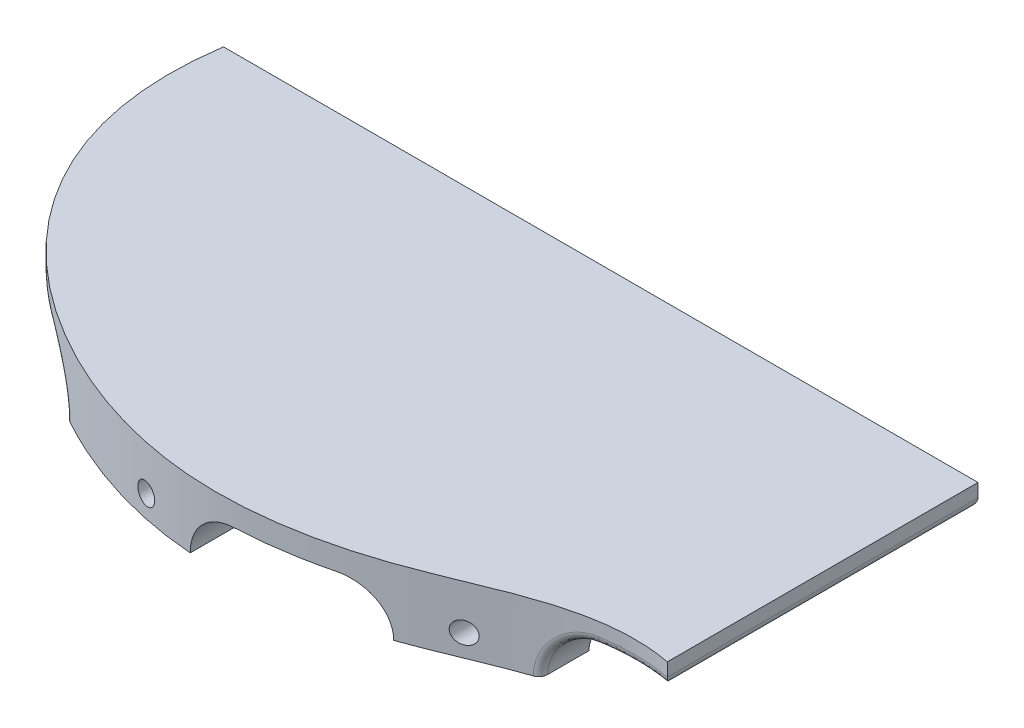
SolidWorks part; units mm, degrees
ref_plane "Front Plane" through (0, 0, 0) normal (0, 0, 1) x (1, 0, 0)
ref_plane "Top Plane" through (0, 0, 0) normal (0, 1, 0) x (1, 0, 0)
ref_plane "Right Plane" through (0, 0, 0) normal (1, 0, 0) x (0, 0, -1)
sketch "Sketch1" plane through (0, 0, 0) normal (0, 1, 0) x (1, 0, 0)
  line L0 (0, 0) -> (107.95, 0)
  line L1 (107.95, 0) -> (107.95, -44.45)
  spline S0 degree 3 poles (0, 0) (-3.3136, -22.2271) (14.8208, -45.9721) (50.3419, -57.703) (79.2202, -52.8256) (96.1348, -42.2193) (107.95, -44.45) knots 0 0 0 0 0.39677 0.585195 0.766956 1 1 1 1
  dimension "D1" = 107.95
  dimension "D2" = 44.45
  dimension "D3" = 12.7
  dimension "D4" = 25.4
  dimension "D5" = 50.8
  dimension "D6" = 76.2
  dimension "D7" = 91.44
  dimension "D8" = 38.1
  dimension "D9" = 47.625
  dimension "D10" = 45.974
  dimension "D11" = 51.8477
  dimension "D12" = 55.5625
extrude "Boss-Extrude1" add sketch "Sketch1" along normal blind 3.175
sketch "Sketch2" plane through (0, 0, 0) normal (0, -1, 0) x (1, 0, 0)
  line L1 (50.8, 42.8625) -> (25.4, 42.8625)
  line L2 (50.8, 42.8625) -> (50.8, 55.5625)
  line L3 (50.8, 55.5625) -> (25.4, 55.5625)
  line L4 (25.4, 42.8625) -> (25.4, 55.5625)
  line L6 (91.44, 39.1478) -> (76.2, 39.1478)
  line L7 (91.44, 39.1478) -> (91.44, 51.8477)
  line L8 (91.44, 51.8477) -> (76.2, 51.8477)
  line L9 (76.2, 39.1478) -> (76.2, 51.8477)
  spline S0 degree 3 poles (0, 0) (-3.3136, 22.2271) (14.8208, 45.9721) (50.3419, 57.703) (79.2202, 52.8256) (96.1348, 42.2193) (107.95, 44.45) knots 0 0 0 0 0.39677 0.585195 0.766956 1 1 1 1
  spline S1 degree 3 poles (0, 0) (-3.3136, 22.2271) (14.8208, 45.9721) (50.3419, 57.703) (79.2202, 52.8256) (96.1348, 42.2193) (107.95, 44.45) knots 0 0 0 0 0.39677 0.585195 0.766956 1 1 1 1 construction
  spline M5 degree 3 poles (107.95, 44.45) (96.1348, 42.2193) (79.2202, 52.8256) (50.3419, 57.703) (14.8208, 45.9721) (-3.3136, 22.2271) (0, 0) knots 0 0 0 0 0.233044 0.414805 0.60323 1 1 1 1
  dimension "D1" = 12.7
  dimension "D2" = 25.4
  dimension "D3" = 50.8
  dimension "D4" = 76.2
  dimension "D5" = 91.44
  dimension "D6" = 25.4
  dimension "D7" = 50.8
  dimension "D8" = 12.7
  dimension "D10" = 15.24
  dimension "D11" = 12.7
extrude "Boss-Extrude2" add sketch "Sketch2" along normal blind 6.35 contours L9 L6 L7 M5 | L4 L1 L2 M5
fillet "Fillet2" radius 6.35 8 edges at (76.2, -3.175, 51.8478) (76.2, -3.175, 39.1478) (91.44, 0, 42.5609) (91.44, -3.175, 39.1478) (91.44, -3.175, 45.974) (76.2, 0, 45.4978) (83.82, 0, 39.1478)
fillet "Fillet3" radius 6.35 8 edges at (25.4, -3.175, 47.625) (25.4, -3.175, 42.8625) (50.8, 0, 49.2125) (50.8, -3.175, 42.8625) (50.8, -3.175, 55.5625) (25.4, 0, 45.2437) (38.1, 0, 42.8625)
sketch "Sketch3" plane through (0, 0, 0) normal (0, 0, -1) x (-1, 0, 0)
  line L0 (-107.95, 3.175) -> (-107.95, 0) construction
  line L1 (-107.95, 3.175) -> (0, 3.175) construction
  circle A0 centre (-83.45, -3.175) radius 1.524
  circle A1 centre (-43.45, -3.175) radius 1.524
  dimension "D4" = 3.048
  dimension "D1" = 40
  dimension "D2" = 24.5
  dimension "D3" = 6.35
extrude "Cut-Extrude1" cut sketch "Sketch3" against normal blind 13.97 from offset 40.64 contours A0 offset against normal yes
sketch "Sketch4" plane through (0, 0, 0) normal (0, 0, -1) x (-1, 0, 0)
  line L0 (-107.95, 3.175) -> (0, 3.175) construction
  circle A0 centre (-43.45, -3.175) radius 1.524
  circle A1 centre (-83.45, -3.175) radius 1.524 construction
  dimension "D1" = 3.048
  dimension "D2" = 40
  dimension "D3" = 6.35
extrude "Cut-Extrude2" cut sketch "Sketch4" against normal blind 13.97 from offset 45.72 offset against normal yes
fillet "Fillet4" radius 1.27 7 edges at (53.975, 0, 0) (92.7281, -2.5159, 45.571) (107.95, 0, 22.225) (23.4612, -1.7823, 46.4832)
